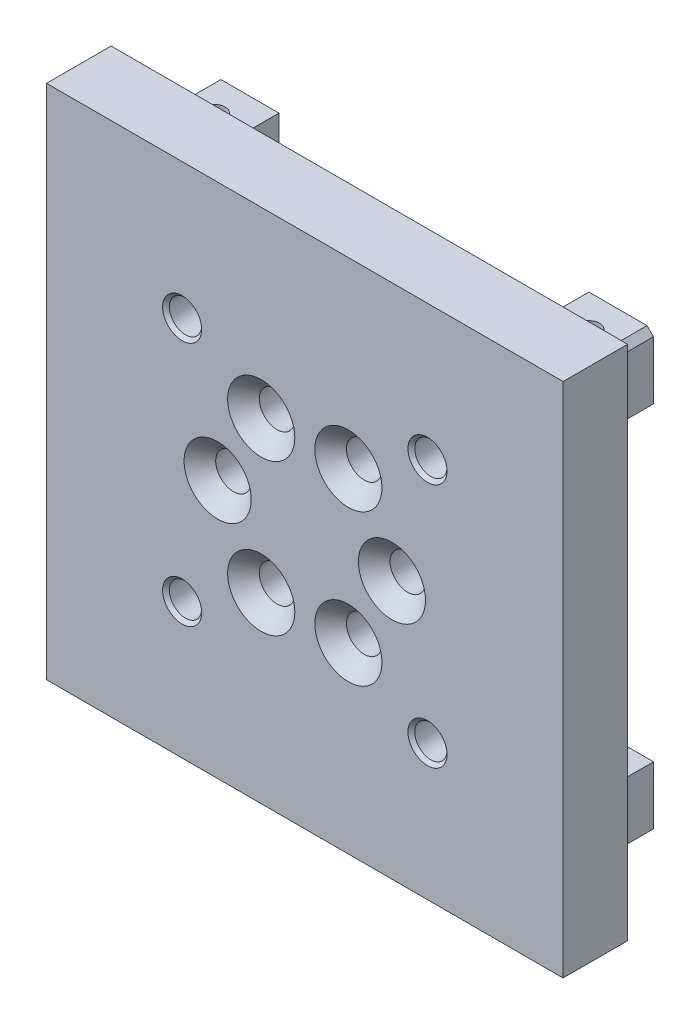
SolidWorks part; units mm, degrees
material "5052-O"
ref_plane "정면" through (0, 0, 0) normal (0, 0, 1) x (1, 0, 0)
ref_plane "윗면" through (0, 0, 0) normal (0, 1, 0) x (1, 0, 0)
ref_plane "우측면" through (0, 0, 0) normal (1, 0, 0) x (0, 0, -1)
sketch "스케치1" plane through (0, 0, 0) normal (0, 0, 1) x (1, 0, 0)
  line L1 (-40, 40) -> (40, 40)
  line L2 (-40, 40) -> (-40, -40)
  line L3 (-40, -40) -> (40, -40)
  line L4 (40, 40) -> (40, -40)
  line L5 (-40, 40) -> (40, -40) construction
  line L6 (-40, -40) -> (40, 40) construction
  point P0 (0, 0)
  dimension "D1" = 80
  dimension "D2" = 80
extrude "보스-돌출1" add sketch "스케치1" along normal blind 10
ref_axis "기준축1" through (0, 0, 0) along (0, 0, 1)
sketch "스케치11" plane through (0, 0, 0) normal (0, 0, -1) x (-1, 0, 0)
  line L0 (40, 40) -> (40, -40) construction
  line L1 (34, 34) -> (24, 34)
  line L2 (34, 34) -> (34, 24)
  line L3 (34, 24) -> (24, 24)
  line L4 (24, 34) -> (24, 24)
  line L5 (34, 34) -> (24, 24) construction
  line L6 (34, 24) -> (24, 34) construction
  line L7 (-40, 40) -> (40, 40) construction
  point P0 (29, 29)
  dimension "D1" = 10
  dimension "D2" = 10
  dimension "D3" = 6
  dimension "D4" = 6
extrude "보스-돌출3" add sketch "스케치11" along normal blind 10
hole_wizard "M4 나사 구멍2" positions "스케치12" profile "스케치13" tap size "M4" standard "ISO" end condition up to next
sketch "스케치12" plane through (0, 34, 0) normal (0, 1, 0) x (1, 0, 0)
  line L0 (-34, 10) -> (-34, 0) construction
  line L1 (-34, 10) -> (-24, 10) construction
  point P0 (-29, 5)
  point P6 (-34, 5)
  point P9 (-29, 10)
sketch "스케치13" plane through (-29, 34, -5) normal (1, 0, 0) x (0, 0, 1)
  line L0 (0, 0) -> (0, 68)
  line L1 (0, 68) -> (1.65, 68)
  line L2 (1.65, 68) -> (1.65, 0)
  line L5 (1.65, 0) -> (0, 0)
  line L11 (0, -6.35) -> (0, 107.95) construction
  dimension "관통 탭 드릴 지름" = 3.3
  dimension "관통 탭 드릴 깊이" = 68
cosmetic thread "구멍 나사산5" parameters "D2"=4
hole_wizard "M5 접시 머리 나사용 카운터싱크1" positions "스케치14" profile "스케치15" countersink size "M5" standard "ISO" end condition up to next
sketch "스케치14" plane through (0, 0, 10) normal (0, 0, 1) x (1, 0, 0)
  line L14 (-13.5, 0) -> (-6.75, -11.6913)
  line L15 (-6.75, -11.6913) -> (6.75, -11.6913)
  line L16 (6.75, -11.6913) -> (13.5, 0)
  line L17 (13.5, 0) -> (6.75, 11.6913)
  line L18 (6.75, 11.6913) -> (-6.75, 11.6913)
  line L19 (-6.75, 11.6913) -> (-13.5, 0)
  line L20 (-40, -40) -> (40, -40) construction
  circle A1 centre (0, 0) radius 13.5 construction
  point P25 (-13.5, 0)
  point P26 (-6.75, -11.6913)
  point P27 (6.75, -11.6913)
  point P28 (13.5, 0)
  point P29 (6.75, 11.6913)
  point P30 (-6.75, 11.6913)
  dimension "D1" = 27
sketch "스케치15" plane through (-6.75, 11.6913, 10) normal (1, 0, 0) x (0, -1, 0)
  line L0 (0, 0) -> (0, 10)
  line L1 (0, 10) -> (2.75, 10)
  line L2 (2.75, 10) -> (2.75, 2.45)
  line L3 (2.75, 2.45) -> (5.2, 0)
  line L5 (5.2, 0) -> (0, 0)
  line L6 (-2.75, 2.45) -> (-5.2, 0) construction
  line L11 (0, -6.35) -> (0, 107.95) construction
  dimension "관통 구멍 지름" = 5.5
  dimension "관통 구멍 깊이" = 10
  dimension "표면 카운터싱크 지름" = 10.4
  dimension "표면 카운터싱크 각도" = 90
hole_wizard "M6 나사 구멍1" positions "스케치16" profile "스케치17" tap size "M6" standard "ISO" end condition up to next
sketch "스케치16" plane through (0, 0, 10) normal (0, 0, 1) x (1, 0, 0)
  line L1 (19, -19) -> (19, 19)
  line L2 (19, 19) -> (-19, 19)
  line L3 (-19, 19) -> (-19, -19)
  line L4 (-19, -19) -> (19, -19)
  line L5 (40, 40) -> (-40, 40) construction
  circle A0 centre (0, 0) radius 19 construction
  point P21 (19, -19)
  point P22 (19, 19)
  point P23 (-19, 19)
  point P24 (-19, -19)
  dimension "D1" = 38
sketch "스케치17" plane through (-19, -19, 10) normal (1, 0, 0) x (0, -1, 0)
  line L0 (0, 0) -> (0, 10)
  line L1 (0, 10) -> (2.5, 10)
  line L2 (2.5, 10) -> (2.5, 0.525)
  line L3 (2.5, 0.525) -> (3.025, 0)
  line L5 (3.025, 0) -> (0, 0)
  line L6 (-2.5, 0.525) -> (-3.025, 0) construction
  line L11 (0, -6.35) -> (0, 107.95) construction
  dimension "관통 탭 드릴 지름" = 5
  dimension "관통 탭 드릴 깊이" = 10
  dimension "표면 카운터싱크 지름" = 6.05
  dimension "표면 카운터싱크 각도" = 90
cosmetic thread "구멍 나사산9" parameters "D2"=6
cosmetic thread "구멍 나사산10" parameters "D2"=6
cosmetic thread "구멍 나사산11" parameters "D2"=6
cosmetic thread "구멍 나사산12" parameters "D2"=6
mirror "대칭 복사1" about plane through (0, 0, 0) normal (1, 0, 0) of "M4 나사 구멍2", "보스-돌출3"
cosmetic thread "구멍 나사산6" parameters "D2"=4
mirror "대칭 복사2" about plane through (0, 0, 0) normal (0, 1, 0) of "대칭 복사1"
cosmetic thread "구멍 나사산7" parameters "D2"=4
cosmetic thread "구멍 나사산8" parameters "D2"=4
chamfer "모따기1" distance 1 angle 45 4 edges at (-34, 34, -5) (34, 34, -5) (34, -34, -5) (-34, -34, -5)
equation "\"D2@스케치1\"=\"D1@스케치1\""
equation "\"D2@스케치11\"=\"D1@스케치11\""
equation "\"D4@스케치11\"=\"D3@스케치11\""
